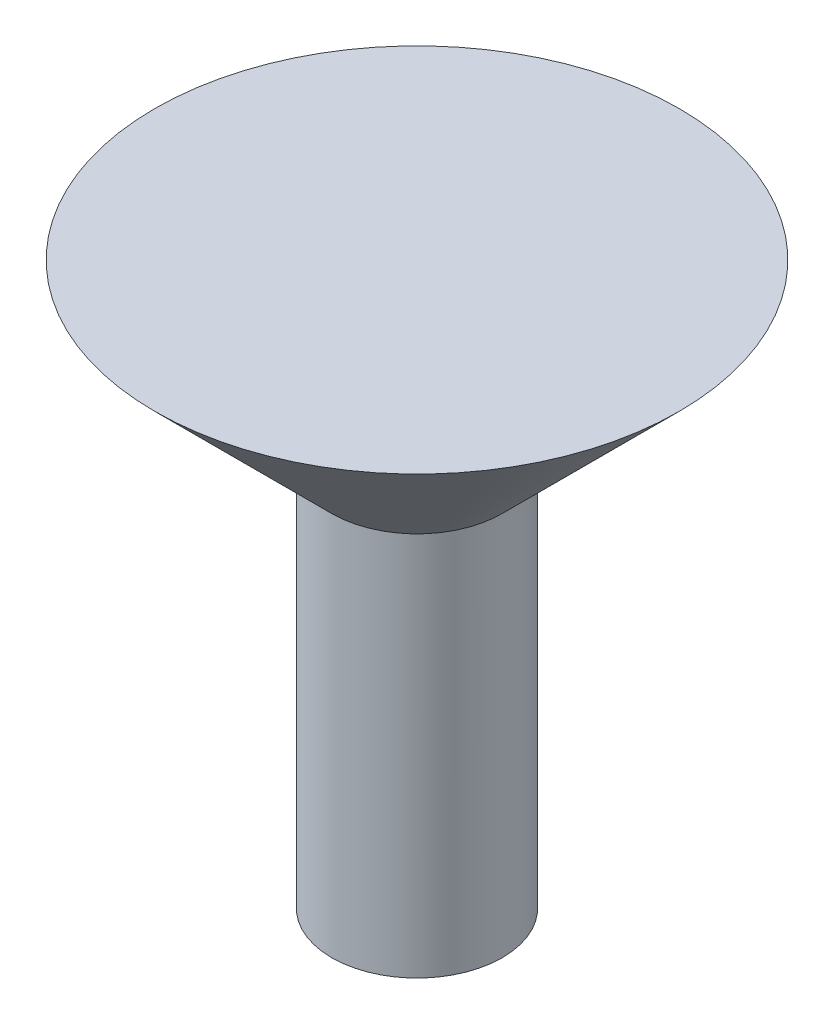
SolidWorks part; units mm, degrees
ref_plane "Front Plane" through (0, 0, 0) normal (0, 0, 1) x (1, 0, 0)
ref_plane "Top Plane" through (0, 0, 0) normal (0, 1, 0) x (1, 0, 0)
ref_plane "Right Plane" through (0, 0, 0) normal (1, 0, 0) x (0, 0, -1)
sketch "Sketch1" plane through (0, 0, 0) normal (0, 0, 1) x (1, 0, 0)
  line L0 (0, 2.5) -> (0, -2.5) construction
  line L1 (0, -2.5) -> (-2.5, -2.5) construction
  line L2 (-2.5, -2.5) -> (-7.5, 2.5) construction
  line L3 (-7.5, 2.5) -> (0, 2.5) construction
  line L4 (-0.2, 2.3) -> (-0.2, -2.3)
  line L5 (-0.2, -2.3) -> (-2.4172, -2.3)
  line L6 (-2.4172, -2.3) -> (-7.0172, 2.3)
  line L7 (-7.0172, 2.3) -> (-0.2, 2.3)
  dimension "D1" = 5
  dimension "D2" = 7.5
  dimension "D3" = 2.5
  dimension "D4" = 0.2
revolve "Revolve1" add sketch "Sketch1" angle 360 about L4
sketch "Sketch2" plane through (0, -2.3, 0) normal (0, -1, 0) x (1, 0, 0)
  circle A1 centre (-0.2, 0) radius 2.2172
  circle A2 centre (-0.2, 0) radius 2.2172
  dimension "D1" = 0
extrude "Boss-Extrude1" add sketch "Sketch2" along normal blind 10
sketch "Sketch3" plane through (0, -12.3, 0) normal (0, -1, 0) x (1, 0, 0)
  circle A0 centre (-0.2, 0) radius 1.7
  circle A1 centre (-0.2, 0) radius 2.2172 construction
  dimension "D1" = 3.4
extrude "Boss-Extrude2" add sketch "Sketch3" against normal blind 3
extrude "Cut-Extrude1" cut sketch "Sketch3<2>" against normal blind 3
sketch "Sketch3<2>" plane through (0, -12.3, 0) normal (0, -1, 0) x (1, 0, 0) same geometry as "Sketch3"
